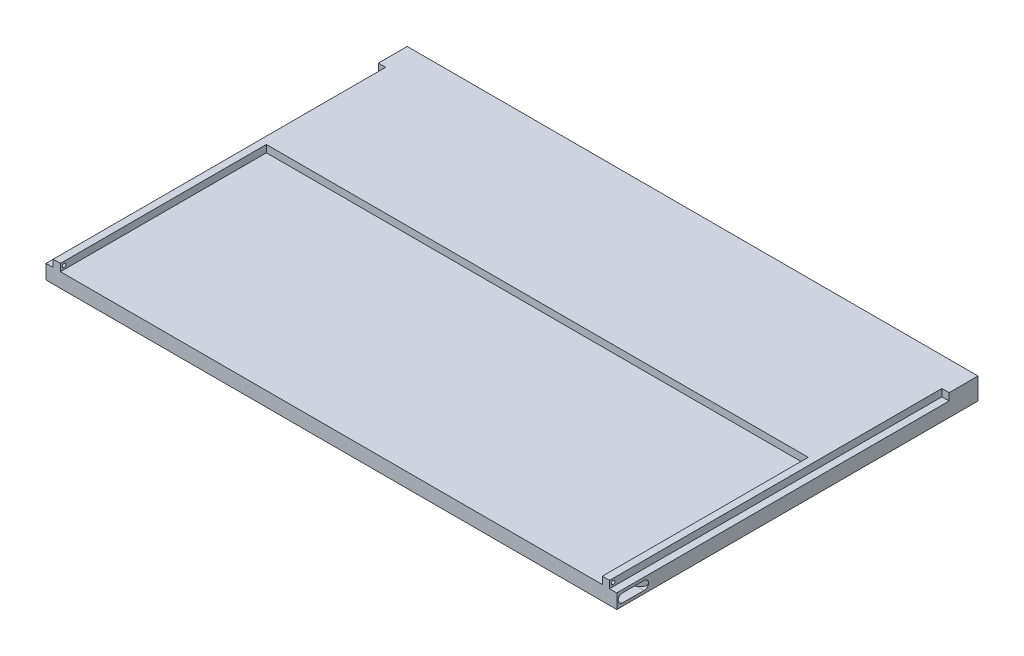
SolidWorks part; units mm, degrees
other "Markup1"
sketch "Sketch12" plane through (250.825, 22.225, 158.75) normal (0.1153, 0.0728, 0.9907) x (0.9687, -0.2289, -0.0959)
material "6061 Alloy"
ref_plane "Front Plane" through (0, 0, 0) normal (0, 0, 1) x (1, 0, 0)
ref_plane "Top Plane" through (0, 0, 0) normal (0, 1, 0) x (1, 0, 0)
ref_plane "Right Plane" through (0, 0, 0) normal (1, 0, 0) x (0, 0, -1)
sketch "Sketch1" plane through (0, 0, 0) normal (0, 1, 0) x (1, 0, 0)
  line L1 (-244.475, 158.75) -> (244.475, 158.75)
  line L2 (-244.475, 158.75) -> (-244.475, -158.75)
  line L3 (-244.475, -158.75) -> (244.475, -158.75)
  line L4 (244.475, 158.75) -> (244.475, -158.75)
  line L5 (-244.475, 158.75) -> (244.475, -158.75) construction
  line L6 (-244.475, -158.75) -> (244.475, 158.75) construction
  point P0 (0, 0)
  dimension "D1" = 488.95
  dimension "D2" = 317.5
extrude "Boss-Extrude1" add sketch "Sketch1" along normal blind 12.7
sketch "Sketch2" plane through (0, 12.7, 0) normal (0, 1, 0) x (1, 0, 0)
  line L0 (-244.475, -158.75) -> (244.475, -158.75) construction
  line L1 (-244.475, 158.75) -> (-238.125, 158.75)
  line L2 (-244.475, 158.75) -> (-244.475, -158.75)
  line L3 (-244.475, -158.75) -> (-238.125, -158.75)
  line L4 (-238.125, 22.225) -> (-238.125, -158.75)
  line L5 (244.475, 158.75) -> (-244.475, 158.75) construction
  line L6 (244.475, 158.75) -> (238.125, 158.75)
  line L7 (244.475, 158.75) -> (244.475, -158.75)
  line L8 (244.475, -158.75) -> (238.125, -158.75)
  line L9 (238.125, 22.225) -> (238.125, -158.75)
  line L10 (-238.125, 158.75) -> (238.125, 158.75)
  line L12 (-238.125, 22.225) -> (238.125, 22.225)
  point P14 (-241.3, -158.75)
  dimension "D1" = 6.35
  dimension "D2" = 180.975
extrude "Boss-Extrude2" add sketch "Sketch2" along normal blind 6.35
sketch "Sketch3" plane through (-244.475, 0, 0) normal (-1, 0, 0) x (0, 0, 1)
  line L0 (158.75, 19.05) -> (158.75, 0) construction
  line L1 (-158.75, 19.05) -> (158.75, 19.05) construction
  circle A0 centre (155.575, 15.875) radius 1.5875
  dimension "D3" = 3.175
  dimension "D1" = 3.175
  dimension "D2" = 3.175
extrude "Cut-Extrude1" cut sketch "Sketch3" against normal through all
sketch "Sketch4" plane through (0, 0, 158.75) normal (0, 0, 1) x (1, 0, 0)
  line L0 (-244.475, 19.05) -> (-244.475, 0) construction
  line L1 (-244.475, 12.7) -> (-250.825, 12.7)
  line L2 (-244.475, 12.7) -> (-244.475, 0)
  line L3 (-244.475, 0) -> (-250.825, 0)
  line L4 (-250.825, 12.7) -> (-250.825, 0)
  line L5 (-244.475, 0) -> (244.475, 0) construction
  dimension "D1" = 12.7
  dimension "D2" = 6.35
extrude "Boss-Extrude3" add sketch "Sketch4" against normal blind 292.1
sketch "Sketch5" plane through (-244.475, 0, 0) normal (-1, 0, 0) x (0, 0, 1)
  line L0 (-158.75, 0) -> (-133.35, 0) construction
  line L1 (-158.75, 19.05) -> (-133.35, 19.05)
  line L2 (-158.75, 19.05) -> (-158.75, 0)
  line L3 (-158.75, 0) -> (-133.35, 0)
  line L4 (-133.35, 19.05) -> (-133.35, 0)
  line L5 (-133.35, 0) -> (-133.35, 12.7) construction
extrude "Boss-Extrude4" add sketch "Sketch5" along normal up to surface (6.35 mm away) up to face at (-250.825, 6.35, 12.7)
mirror "Mirror1" about plane through (0, 0, 0) normal (1, 0, 0) of "Boss-Extrude4", "Boss-Extrude3"
sketch "Sketch6" plane through (-244.475, 0, 0) normal (-1, 0, 0) x (0, 0, 1)
  line L0 (153.67, 6.35) -> (134.62, 6.35) construction
  line L1 (153.67, 2.54) -> (134.62, 2.54)
  line L2 (153.67, 10.16) -> (134.62, 10.16)
  line L3 (158.75, 19.05) -> (158.75, 12.7) construction
  line L5 (158.75, 12.7) -> (158.75, 0) construction
  arc A0 (153.67, 2.54) -> (153.67, 10.16) centre (153.67, 6.35) ccw
  arc A1 (134.62, 10.16) -> (134.62, 2.54) centre (134.62, 6.35) ccw
  point P2 (144.145, 6.35)
  point P11 (158.75, 6.35)
  dimension "D1" = 19.05
  dimension "D2" = 5.08
  dimension "D3" = 7.62
extrude "Cut-Extrude2" cut sketch "Sketch6" against normal blind 25.4 from surface starting at face at (-250.825, 10.5833, -44.45)
extrude "Cut-Extrude3" cut sketch "Sketch6<2>" along normal blind 25.4 from surface starting at face at (250.825, 10.5833, -44.45)
sketch "Sketch6<2>" plane through (-244.475, 0, 0) normal (-1, 0, 0) x (0, 0, 1) same geometry as "Sketch6"
sketch "Sketch11" plane through (0, 0, 0) normal (0, -1, 0) x (1, 0, 0)
  line L0 (-250.825, 130.81) -> (-225.425, 130.81)
  line L1 (-225.425, 130.81) -> (-225.425, 147.32)
  line L2 (-225.425, 147.32) -> (-250.825, 130.81)
  line L3 (-225.425, 134.62) -> (-225.425, 153.67) construction
  dimension "D1" = 10.16
extrude "Boss-Extrude5" add sketch "Sketch11" against normal up to surface (10.16 mm away) from surface up to face at (-238.125, 10.16, 144.145) starting at face at (-238.125, 2.54, 144.145)
mirror "Mirror2" about plane through (0, 0, 0) normal (1, 0, 0) of "Boss-Extrude5"
